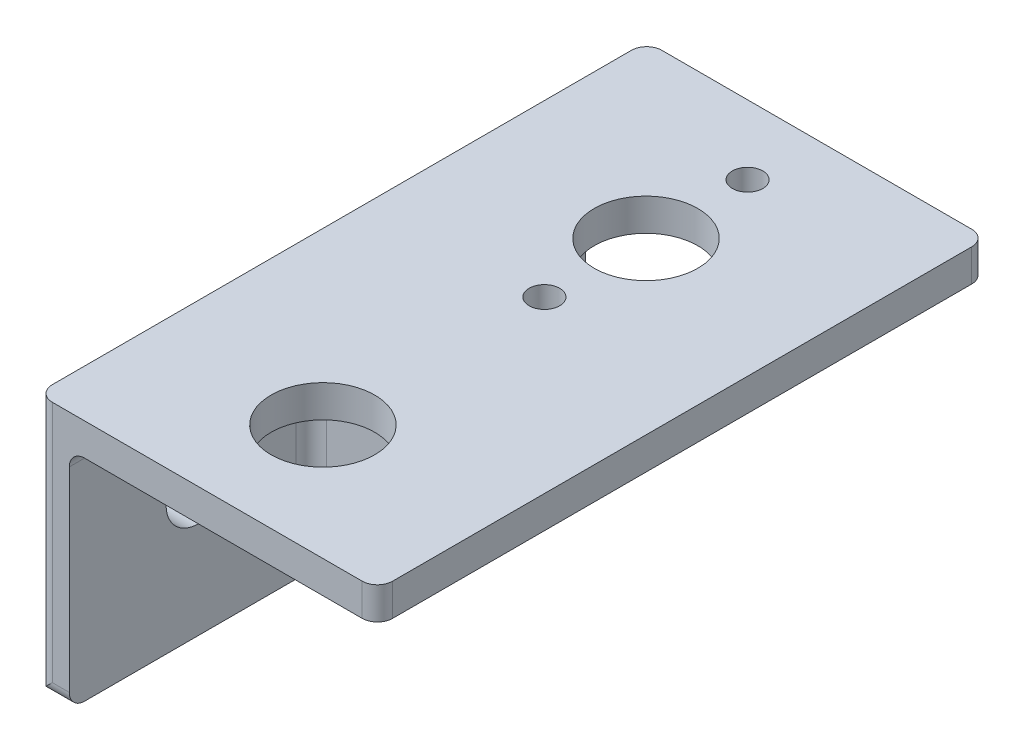
SolidWorks part; units mm, degrees
material "ABS"
ref_plane "Front Plane" through (0, 0, 0) normal (0, 0, 1) x (1, 0, 0)
ref_plane "Top Plane" through (0, 0, 0) normal (0, 1, 0) x (1, 0, 0)
ref_plane "Right Plane" through (0, 0, 0) normal (1, 0, 0) x (0, 0, -1)
sketch "Sketch2" plane through (0, 0, 0) normal (1, 0, 0) x (0, 0, -1)
  line L1 (-25.4, -12.7) -> (25.4, -12.7)
  line L2 (-25.4, -12.7) -> (-25.4, 12.7)
  line L3 (-25.4, 12.7) -> (25.4, 12.7)
  line L4 (25.4, -12.7) -> (25.4, 12.7)
  line L5 (-25.4, -12.7) -> (25.4, 12.7) construction
  line L6 (-25.4, 12.7) -> (25.4, -12.7) construction
  point P0 (0, 0)
  dimension "D1" = 25.4
  dimension "D2" = 50.8
extrude "Boss-Extrude1" add sketch "Sketch2" along normal blind 3.175
sketch "Sketch4" plane through (0, 12.7, 0) normal (0, 1, 0) x (1, 0, 0)
  line L1 (0, 34.6) -> (33.5, 34.6)
  line L2 (0, 34.6) -> (0, -25.4)
  line L3 (0, -25.4) -> (33.5, -25.4)
  line L4 (33.5, 34.6) -> (33.5, -25.4)
  dimension "D1" = 60
  dimension "D2" = 33.5
extrude "Boss-Extrude2" add sketch "Sketch4" against normal blind 3.175
sketch "Sketch6" plane through (0, 0, 0) normal (-1, 0, 0) x (0, 0, 1)
  line L0 (12.7, 0) -> (-12.7, 0) construction
  circle A0 centre (-12.7, 0) radius 3.175
  circle A1 centre (12.7, 0) radius 3.175
  point P4 (0, 0)
extrude "Cut-Extrude2" cut sketch "Sketch6" against normal blind 3.175
sketch "Sketch7" plane through (0, 0, 0) normal (0, 0, 1) x (1, 0, 0)
  line L2 (3.175, -12.7) -> (25.4, 9.525)
  line L3 (3.175, 9.525) -> (33.5, 9.525) construction
  line L8 (3.175, -12.7) -> (3.175, 9.525)
  line L9 (25.4, 9.525) -> (3.175, 9.525)
extrude "Boss-Extrude3" add sketch "Sketch7" along normal mid plane 3.175
sketch "Sketch8" plane through (0, 12.7, 0) normal (0, 1, 0) x (1, 0, 0)
  line L0 (16.75, 21.85) -> (16.75, 2.3144) construction
  circle A15 centre (16.75, 17.7881) radius 16.75 construction
  circle A16 centre (16.75, 17.7881) radius 5.1
  circle A17 centre (16.75, 17.7881) radius 10 construction
  circle A18 centre (16.75, 7.7881) radius 1.5
  circle A19 centre (16.75, 27.7881) radius 1.5
  circle A20 centre (16.75, 7.7881) radius 6 construction
  circle A21 centre (16.75, 27.7881) radius 6 construction
  circle A22 centre (16.75, -14.0144) radius 5.1
extrude "Cut-Extrude3" cut sketch "Sketch8" against normal blind 10
fillet "Fillet3" radius 1.5 13 edges at (3.175, -1.5875, -1.5875) (14.2875, 9.525, -1.5875) (25.4, 9.525, 0) (3.175, -1.5875, 1.5875) (14.2875, 9.525, 1.5875) (3.175, 9.525, 13.4937) (3.175, 9.525, -13.4937) (1.5875, -12.7, 25.4) (1.5875, -12.7, -25.4) (33.5, 11.1125, 25.4) (33.5, 11.1125, -34.6) (0, 0, 25.4) (0, 11.1125, -34.6)
